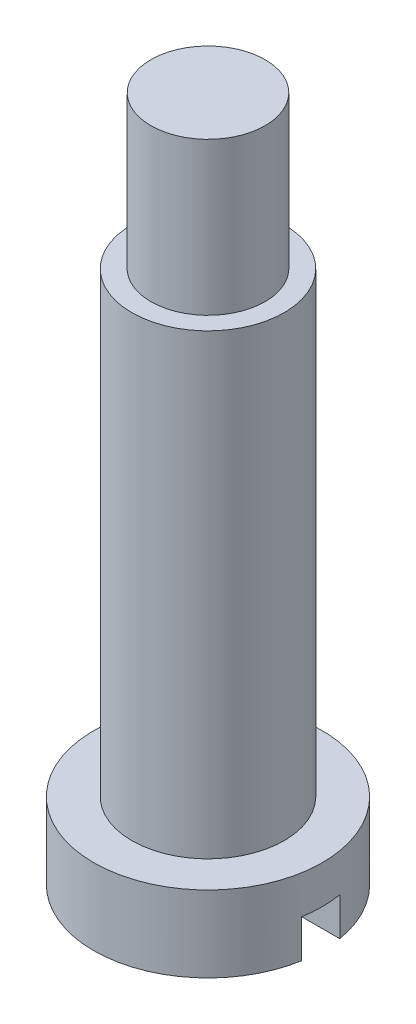
SolidWorks part; units mm, degrees
ref_plane "前视基准面" through (0, 0, 0) normal (0, 0, 1) x (1, 0, 0)
ref_plane "上视基准面" through (0, 0, 0) normal (0, 1, 0) x (1, 0, 0)
ref_plane "右视基准面" through (0, 0, 0) normal (1, 0, 0) x (0, 0, -1)
other "Configuration Table"
sketch "草图1" plane through (0, 0, 0) normal (0, 1, 0) x (1, 0, 0)
  circle A0 centre (0, 0) radius 3
  dimension "D1" = 6
extrude "凸台-拉伸1" add sketch "草图1" against normal blind 2
sketch "草图2" plane through (0, 0, 0) normal (0, 1, 0) x (1, 0, 0)
  circle A0 centre (0, 0) radius 2
  dimension "D1" = 4
extrude "凸台-拉伸2" add sketch "草图2" along normal blind 12 contours A0
sketch "草图3" plane through (0, 12, 0) normal (0, 1, 0) x (1, 0, 0)
  circle A0 centre (0, 0) radius 1.5
  dimension "D1" = 3
extrude "凸台-拉伸3" add sketch "草图3" along normal blind 4
sketch "草图4" plane through (0, -2, 0) normal (0, -1, 0) x (1, 0, 0)
  line L0 (-3, 0) -> (3, 0)
  circle A0 centre (0, 0) radius 3 construction
extrude "切除-拉伸-薄壁1" cut sketch "草图4" against normal blind 1 and the other way through all thin thin type mid plane wall 1
ref_axis "基准轴1" through (0, 23.8772, 0) along (0, -1, 0)
